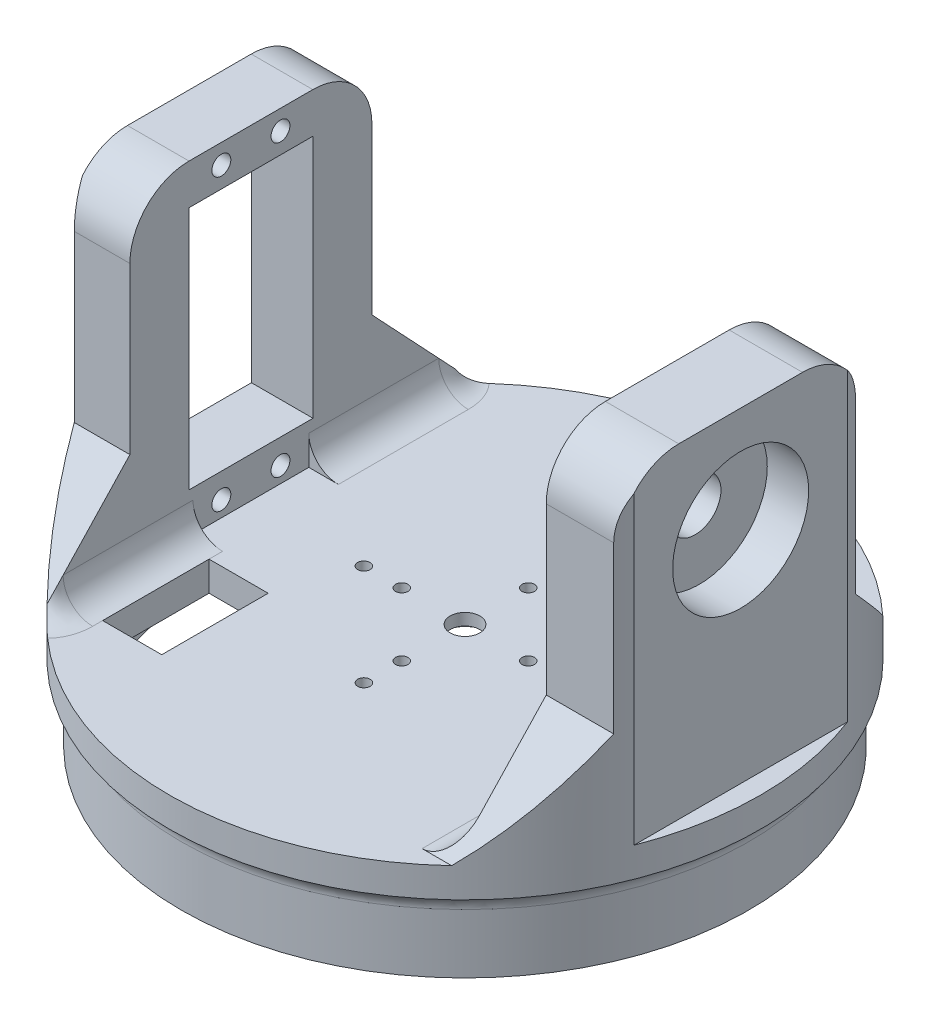
SolidWorks part; units mm, degrees
ref_plane "Front Plane" through (0, 0, 0) normal (0, 0, 1) x (1, 0, 0)
ref_plane "Top Plane" through (0, 0, 0) normal (0, 1, 0) x (1, 0, 0)
ref_plane "Right Plane" through (0, 0, 0) normal (1, 0, 0) x (0, 0, -1)
sketch "Sketch2" plane through (0, 0, 0) normal (0, 1, 0) x (1, 0, 0)
  circle A0 centre (0, 0) radius 50
  dimension "D1" = 100
extrude "Boss-Extrude1" add sketch "Sketch2" along normal blind 5
sketch "Sketch5" plane through (0, 0, 0) normal (0, -1, 0) x (1, 0, 0)
  line L4 (-19.5, 4.3) -> (-4.3, 4.3)
  line L6 (-4.3, 19.5) -> (-4.3, 4.3)
  line L9 (4.3, -19.5) -> (4.3, -4.3)
  line L10 (19.5, -4.3) -> (4.3, -4.3)
  line L12 (4.3, 19.5) -> (4.3, 4.3)
  line L14 (19.5, 4.3) -> (4.3, 4.3)
  line L16 (-19.5, -4.3) -> (-4.3, -4.3)
  line L18 (-4.3, -19.5) -> (-4.3, -4.3)
  arc A0 (-19.5, -4.3) -> (-19.5, 4.3) centre (-19.5, 0) cw
  arc A1 (-4.3, 19.5) -> (4.3, 19.5) centre (0, 19.5) cw
  arc A2 (19.5, 4.3) -> (19.5, -4.3) centre (19.5, 0) cw
  arc A3 (4.3, -19.5) -> (-4.3, -19.5) centre (0, -19.5) cw
  dimension "D1" = 8.6
  dimension "D2" = 8.6
  dimension "D3" = 8.6
  dimension "D4" = 15.2
  dimension "D5" = 15.2
  dimension "D6" = 15.2
  dimension "D7" = 15.2
  dimension "D8" = 8.6
extrude "Cut-Extrude2" cut sketch "Sketch5" against normal blind 2.15
fillet "Fillet3" radius 4 4 edges at (4.3, 1.075, -4.3) (-4.3, 1.075, -4.3) (4.3, 1.075, 4.3) (-4.3, 1.075, 4.3)
sketch "Sketch6" plane through (0, 5, 0) normal (0, 1, 0) x (1, 0, 0)
  line L2 (34.2081, -36.4665) -> (34.2081, 36.4665)
  line L3 (46.6228, -18.0642) -> (46.6228, 18.0642)
  line L4 (-34.2081, -36.4665) -> (-34.2081, 36.4665)
  line L6 (-46.6228, -18.0642) -> (-46.6228, 18.0642)
  circle A0 centre (0, 0) radius 50 construction
  arc A1 (-34.2081, 36.4665) -> (-46.6228, 18.0642) centre (0, 0) ccw
  arc A2 (34.2081, -36.4665) -> (46.6228, -18.0642) centre (0, 0) ccw
  arc A3 (-46.6228, -18.0642) -> (-34.2081, -36.4665) centre (0, 0) ccw
  arc A4 (46.6228, 18.0642) -> (34.2081, 36.4665) centre (0, 0) ccw
  point P0 (0, 0)
  dimension "D1" = 36.1285
extrude "Boss-Extrude2" add sketch "Sketch6" along normal blind 55
sketch "Sketch7" plane through (-34.2081, 0, 0) normal (1, 0, 0) x (0, 0, -1)
  line L1 (0, 60) -> (0, 5)
  line L2 (-36.4665, 60) -> (36.4665, 60) construction
  line L3 (-36.4665, 5) -> (36.4665, 5) construction
  line L4 (36.4665, 60) -> (36.4665, 5) construction
  line L5 (10.5, 11.84) -> (-10.5, 11.84)
  line L6 (10.5, 11.84) -> (10.5, 53.16)
  line L9 (10.5, 53.16) -> (-10.5, 53.16)
  line L10 (-10.5, 11.84) -> (-10.5, 53.16)
  line L11 (10.5, 11.84) -> (-10.5, 53.16) construction
  line L12 (10.5, 53.16) -> (-10.5, 11.84) construction
  point P6 (0, 32.5)
  dimension "D1" = 41.32
  dimension "D2" = 36.4665
  dimension "D3" = 21
extrude "Cut-Extrude3" cut sketch "Sketch7" against normal blind 50 contours L10 L9 L6 L5
sketch "Sketch8" plane through (-34.2081, 0, 0) normal (1, 0, 0) x (0, 0, -1)
  line L0 (10.5, 53.16) -> (-10.5, 53.16) construction
  line L1 (-10.5, 11.84) -> (-10.5, 53.16) construction
  circle A0 centre (-0.71, 42.67) radius 4.375
  dimension "D1" = 8.75
  dimension "D2" = 10.49
  dimension "D3" = 9.79
sketch "Sketch9" plane through (-34.2081, 0, 0) normal (1, 0, 0) x (0, 0, -1)
  line L0 (-36.4665, 60) -> (-36.4665, 5) construction
  line L2 (-36.4665, 5) -> (36.4665, 5) construction
  line L3 (-36.4665, 22) -> (-20.4665, 22)
  line L6 (36.4665, 60) -> (36.4665, 22)
  line L7 (-20.4665, 22) -> (-20.4665, 60)
  line L8 (-36.4665, 60) -> (36.4665, 60) construction
  line L9 (20.4665, 60) -> (36.4665, 60)
  line L10 (20.4665, 22) -> (20.4665, 60)
  line L11 (-20.4665, 60) -> (-36.4665, 60)
  line L12 (36.4665, 22) -> (20.4665, 22)
  line L13 (-36.4665, 60) -> (-36.4665, 22)
  dimension "D1" = 17
  dimension "D2" = 16
extrude "Cut-Extrude5" cut sketch "Sketch9" against normal blind 18.45 and the other way blind 103
fillet "Fillet6" radius 10 4 edges at (-39.9137, 60, -20.4665) (-39.9137, 60, 20.4665) (39.9137, 60, 20.4665) (39.9137, 60, -20.4665)
sketch "Sketch10" plane through (-34.2081, 0, 0) normal (1, 0, 0) x (0, 0, -1)
  line L0 (-20.4665, 22) -> (-36.4665, 5)
  line L1 (-36.4665, 5) -> (-36.4665, 22)
  line L2 (-36.4665, 22) -> (-20.4665, 22)
  line L3 (0, 11.84) -> (0, 8.4378)
  line L4 (10.5, 11.84) -> (-10.5, 11.84) construction
  line L5 (36.4665, 22) -> (20.4665, 22)
  line L6 (36.4665, 5) -> (36.4665, 22)
  line L7 (20.4665, 22) -> (36.4665, 5)
  line M10 (-20.4665, 22) -> (-36.4665, 22)
  line M11 (-36.4665, 22) -> (-36.4665, 5)
  line M13 (36.4665, 5) -> (36.4665, 22)
  line M14 (36.4665, 22) -> (20.4665, 22)
extrude "Cut-Extrude6" cut sketch "Sketch10" against normal blind 18.45 and the other way blind 98.45 contours L0 M10 M11 | L7 M14 M13 region at (-34.2081, 16.3333, 31.1332) region at (-34.2081, 16.3333, -31.1332)
sketch "Sketch11" plane through (0, 2.15, 0) normal (0, -1, 0) x (1, 0, 0)
  circle A0 centre (0, 0) radius 2.5
  dimension "D1" = 5
extrude "Cut-Extrude7" cut sketch "Sketch11" against normal blind 10
sketch "Sketch23" plane through (0, 0, 0) normal (0, -1, 0) x (1, 0, 0)
  circle A0 centre (0, 0) radius 48
  circle A1 centre (0, 0) radius 45
  dimension "D1" = 90
  dimension "D2" = 96
extrude "Boss-Extrude3" add sketch "Sketch23" along normal blind 12.85
sketch "Sketch15" plane through (0, 2.15, 0) normal (0, -1, 0) x (1, 0, 0)
  circle A0 centre (0, 0) radius 3.6
  dimension "D1" = 7.2
extrude "Cut-Extrude9" cut sketch "Sketch15" against normal blind 0.85
fillet "Fillet7" radius 5 1 edges at (34.2081, 5, 0)
sketch "Sketch17" plane through (46.6228, 0, 0) normal (1, 0, 0) x (0, 0, -1)
  circle A0 centre (0, 42.17) radius 11.5
  dimension "D1" = 23
extrude "Cut-Extrude11" cut sketch "Sketch17" against normal blind 7
extrude "Cut-Extrude12" cut sketch "Sketch8" along normal blind 114
sketch "Sketch20" plane through (-34.2081, 0, 0) normal (1, 0, 0) x (0, 0, -1)
  line L1 (-36.4665, 5) -> (46.8417, 5)
  line L2 (-36.4665, 5) -> (-36.4665, 69.1867)
  line L3 (-36.4665, 69.1867) -> (46.8417, 69.1867)
  line L4 (46.8417, 5) -> (46.8417, 69.1867)
extrude "Cut-Extrude14" cut sketch "Sketch20" against normal blind 2
fillet "Fillet8" radius 5 1 edges at (-36.2081, 5, 0)
sketch "Sketch21" plane through (-36.2081, 0, 0) normal (1, 0, 0) x (0, 0, -1)
  line L1 (-9.79, 15) -> (9.79, 15)
  line L2 (-9.79, 15) -> (-9.79, 5)
  line L3 (-9.79, 5) -> (9.79, 5)
  line L4 (9.79, 15) -> (9.79, 5)
  dimension "D1" = 19.58
  dimension "D2" = 10
extrude "Cut-Extrude15" cut sketch "Sketch21" along normal blind 11
sketch "Sketch22" plane through (0, 5, 0) normal (0, 1, 0) x (1, 0, 0)
  line L0 (-31.2081, -10.5) -> (-31.2081, -36.4665) construction
  line L1 (-31.2081, -12.0808) -> (-21.2081, -12.0808)
  line L2 (-31.2081, -12.0808) -> (-31.2081, -30.0808)
  line L3 (-31.2081, -30.0808) -> (-21.2081, -30.0808)
  line L4 (-21.2081, -12.0808) -> (-21.2081, -30.0808)
  dimension "D1" = 10
  dimension "D2" = 18
extrude "Cut-Extrude16" cut sketch "Sketch22" against normal blind 11
sketch "Sketch24" plane through (-46.6228, 0, 0) normal (-1, 0, 0) x (0, 0, 1)
  circle A0 centre (0, 42.17) radius 10.2092
sketch "Sketch25" plane through (-36.2081, 0, 0) normal (1, 0, 0) x (0, 0, -1)
  circle A0 centre (-5, 56.67) radius 1.6
  circle A1 centre (5, 56.67) radius 1.6
  circle A2 centre (-5, 7.67) radius 1.6
  circle A3 centre (5, 7.67) radius 1.6
extrude "Cut-Extrude18" cut sketch "Sketch25" against normal up to next
sketch "Sketch26" plane through (-46.6228, 0, 0) normal (-1, 0, 0) x (0, 0, 1)
  circle A0 centre (-5, 56.67) radius 2.5
  circle A1 centre (5, 56.67) radius 2.5
extrude "Cut-Extrude20" cut sketch "Sketch26" against normal blind 2.5
sketch "Sketch27" plane through (0, 2.15, 0) normal (0, -1, 0) x (1, 0, 0)
  circle A0 centre (-17.1, 0) radius 1.05
  circle A1 centre (0, 17.1) radius 1.05
  circle A2 centre (0, -17.1) radius 1.05
  circle A3 centre (17.1, 0) radius 1.05
  circle A4 centre (0, 10.7) radius 1.05
  circle A5 centre (0, -10.7) radius 1.05
  circle A6 centre (-10.7, 0) radius 1.05
  circle A7 centre (10.7, 0) radius 1.05
extrude "Cut-Extrude21" cut sketch "Sketch27" against normal up to next
fillet "Fillet9" radius 3 2 edges at (0, 0, -45) (0, 0, 48)
